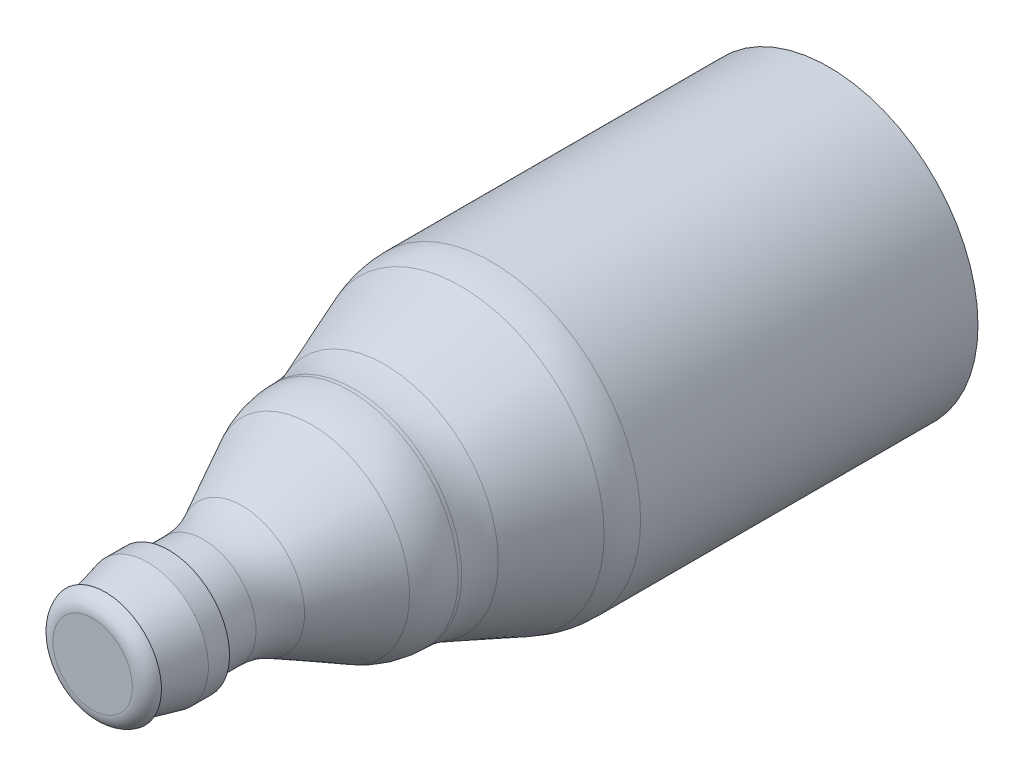
SolidWorks part; units mm, degrees
ref_plane "Plan de face" through (0, 0, 0) normal (0, 0, 1) x (1, 0, 0)
ref_plane "Plan de dessus" through (0, 0, 0) normal (0, 1, 0) x (1, 0, 0)
ref_plane "Plan de droite" through (0, 0, 0) normal (1, 0, 0) x (0, 0, -1)
sketch "Esquisse1" plane through (0, 0, 0) normal (0, 0, 1) x (1, 0, 0)
  circle A0 centre (0, 0) radius 35.25
  dimension "D1" = 70.5
extrude "Boss.-Extru.1" add sketch "Esquisse1" along normal blind 10
sketch "Esquisse2" plane through (0, 0, 0) normal (0, 1, 0) x (1, 0, 0)
  line L0 (0, 0) -> (0, -80.0387) construction
  line L1 (0, 0) -> (-35.25, 0)
  line L2 (-35.25, 0) -> (-35.25, -83.5)
  line L3 (-35.25, -83.5) -> (-25.5, -108.5)
  line L4 (-25.5, -108.5) -> (-25.5, -118)
  line L5 (-25.5, -118) -> (-12.5, -143)
  line L6 (-12.5, -143) -> (-12.5, -156)
  line L7 (-12.5, -156) -> (-14.35, -156)
  line L8 (-14.35, -156) -> (-14.35, -161)
  line L9 (-14.35, -161) -> (-12, -171)
  line L10 (-12, -171) -> (-13.25, -171)
  line L11 (-13.25, -171) -> (-12.5, -174)
  line L12 (-12.5, -174) -> (0, -174)
  line L13 (0, 0) -> (0, -174)
  dimension "D1" = 83.5
  dimension "D2" = 70.5
  dimension "D3" = 31
  dimension "D4" = 156
  dimension "D5" = 174
  dimension "D6" = 25
  dimension "D7" = 25
  dimension "D8" = 25
  dimension "D9" = 14.35
  dimension "D10" = 13.25
  dimension "D11" = 12
  dimension "D12" = 15
  dimension "D13" = 5
  dimension "D14" = 25.5
  dimension "D15" = 56
revolve "Révolution1" add sketch "Esquisse2" angle 360 about L0
fillet "Congé1" radius 4 1 edges at (-12.5, 0, 174)
fillet "Congé2" radius 20 4 edges at (-25.5, 0, 108.5) (-35.25, 0, 83.5) (-25.5, 0, 118) (-12.5, 0, 143)
sketch "Esquisse3" plane through (0, 0, 0) normal (0, 0, -1) x (-1, 0, 0)
  point P0 (0, 0)
